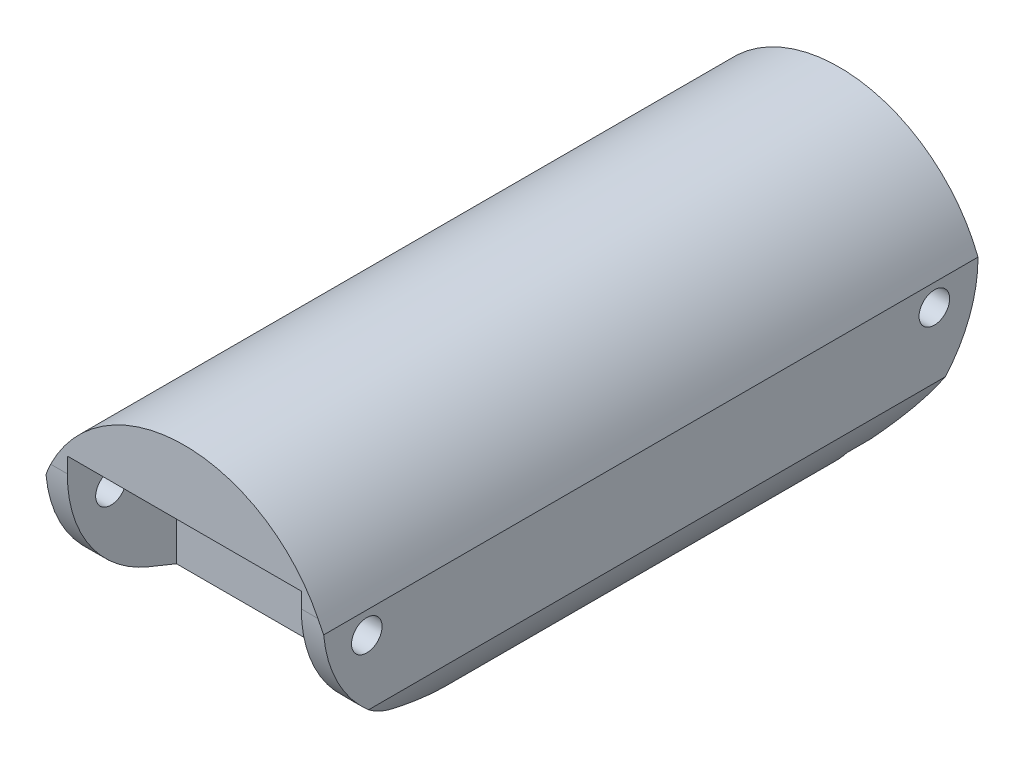
SolidWorks part; units mm, degrees
material "PET"
ref_plane "Front Plane" through (0, 0, 0) normal (0, 0, 1) x (1, 0, 0)
ref_plane "Top Plane" through (0, 0, 0) normal (0, 1, 0) x (1, 0, 0)
ref_plane "Right Plane" through (0, 0, 0) normal (1, 0, 0) x (0, 0, -1)
sketch "Sketch1" plane through (0, 0, 0) normal (0, 0, 1) x (1, 0, 0)
  line L0 (0, 0) -> (0, 5.08)
  line L3 (16.1544, 5.08) -> (16.1544, 0)
  arc A2 (0, 5.08) -> (16.1544, 5.08) centre (8.0772, 1.9574) cw
  arc A3 (0, 0) -> (16.1544, 0) centre (8.0772, 3.1226) ccw
  point P7 (8.0772, -5.5372)
  point P8 (8.0772, 10.6172)
  dimension "D1" = 16.1544
  dimension "D2" = 16.1544
  dimension "D3" = 5.08
extrude "Boss-Extrude1" add sketch "Sketch1" along normal mid plane 38.1 contours A2 L3 A3 L0
sketch "Sketch2" plane through (0, 0, 0) normal (1, 0, 0) x (0, 0, -1)
  line L4 (15.875, 2.54) -> (-49984.125, 2.54) construction
  line L5 (19.05, 5.08) -> (19.05, 0) construction
  line L6 (-19.05, 5.08) -> (-19.05, 0) construction
  line L7 (-19.05, -5.5372) -> (-19.05, 0.635)
  line L8 (-3.81, -5.5372) -> (-19.05, -5.5372)
  line L9 (-19.05, 0.635) -> (-3.81, -5.5372)
  line L10 (0, -1000) -> (0, 49000) construction
  line L18 (19.05, 0.635) -> (19.05, -5.5372)
  line L19 (-16.51, 1.27) -> (-19.05, 1.27)
  line L21 (-16.51, 3.81) -> (-19.05, 3.81)
  line L22 (-19.05, 1.27) -> (-19.05, 3.81)
  line L23 (-15.0884, 2.54) -> (-19.05, 3.81) construction
  line L24 (-15.0884, 2.54) -> (-19.05, 1.27) construction
  line L27 (16.51, 1.27) -> (19.05, 1.27)
  line L28 (19.05, 1.27) -> (19.05, 3.81)
  line L29 (16.51, 3.81) -> (19.05, 3.81)
  line L30 (19.05, -5.5372) -> (8.3594, -5.5372)
  line L31 (-19.05, -5.5372) -> (19.05, -5.5372) construction
  line L32 (8.3594, -5.5372) -> (19.05, 0.635)
  line L33 (-19.05, 10.6172) -> (-19.05, 5.08) construction
  arc A3 (-16.51, 3.81) -> (-16.51, 1.27) centre (-14.3103, 2.54) cw
  arc A4 (16.51, 3.81) -> (16.51, 1.27) centre (14.3103, 2.54) ccw
  point P0 (-15.0884, 2.54)
  point P11 (19.05, 2.54)
  point P14 (-19.05, 2.54)
  point P26 (-19.05, 2.54)
  dimension "D3" = 2.54
  dimension "D4" = 0.635
  dimension "D5" = 60
  dimension "D6" = 0.635
  dimension "D1" = 3.81
extrude "Cut-Extrude1" cut sketch "Sketch2" along normal through all
sketch "Sketch3" plane through (0, 0, 19.05) normal (0, 0, 1) x (1, 0, 0)
  line L3 (-11.7804, 2.54) -> (36.5812, 2.54) construction
  line L4 (8.0772, 9.0576) -> (8.0772, -5.5372) construction
  line L5 (16.1544, 2.54) -> (0, 2.54) construction
  line L6 (16.1544, 2.54) -> (0, 2.54) construction
  line L7 (0, 5.08) -> (0, 0) construction
  line L8 (16.1544, 0.635) -> (0, 0.635) construction
  arc A7 (0, 0) -> (16.1544, 0) centre (8.0772, 3.1226) ccw construction
  arc A9 (14.6124, 0.635) -> (1.542, 0.635) centre (8.0772, 2.54) cw
  arc A13 (5.4577, -3.743) -> (10.6967, -3.743) centre (8.0772, -5.5372) cw
  dimension "D1" = 1.27
  dimension "D2" = 3.175
extrude "Cut-Extrude2" cut sketch "Sketch3" against normal through all contours A13 A9
sketch "Sketch4" plane through (0, 0, 0) normal (-1, 0, 0) x (0, 0, 1)
  line L0 (19.05, 1.27) -> (16.51, 1.27) construction
  line L1 (16.51, 3.81) -> (19.05, 3.81) construction
  line L2 (-16.51, 1.27) -> (-19.05, 1.27) construction
  line L3 (-19.05, 3.81) -> (-16.51, 3.81) construction
  line L4 (19.05, 1.27) -> (16.51, 1.27)
  line L5 (16.51, 3.81) -> (19.05, 3.81)
  line L6 (-16.51, 1.27) -> (-19.05, 1.27)
  line L7 (-19.05, 3.81) -> (-16.51, 3.81)
  line L8 (-19.05, 3.81) -> (-19.05, 1.27)
  line L9 (19.05, 3.81) -> (19.05, 1.27)
  arc A0 (14.3103, 0) -> (16.51, 1.27) centre (14.3103, 2.54) ccw construction
  arc A1 (16.51, 3.81) -> (14.3103, 5.08) centre (14.3103, 2.54) ccw construction
  arc A2 (14.3103, 5.08) -> (14.3103, 0) centre (14.3103, 2.54) ccw construction
  arc A3 (-16.51, 1.27) -> (-14.3103, 0) centre (-14.3103, 2.54) ccw construction
  arc A4 (-14.3103, 5.08) -> (-16.51, 3.81) centre (-14.3103, 2.54) ccw construction
  arc A5 (-14.3103, 0) -> (-14.3103, 5.08) centre (-14.3103, 2.54) ccw construction
  arc A6 (14.3103, 0) -> (16.51, 1.27) centre (14.3103, 2.54) ccw
  arc A7 (16.51, 3.81) -> (14.3103, 5.08) centre (14.3103, 2.54) ccw
  arc A8 (14.3103, 5.08) -> (14.3103, 0) centre (14.3103, 2.54) ccw
  arc A9 (-16.51, 1.27) -> (-14.3103, 0) centre (-14.3103, 2.54) ccw
  arc A10 (-14.3103, 5.08) -> (-16.51, 3.81) centre (-14.3103, 2.54) ccw
  arc A11 (-14.3103, 0) -> (-14.3103, 5.08) centre (-14.3103, 2.54) ccw
extrude "Boss-Extrude2" add sketch "Sketch4" against normal up to surface (16.1544 mm away) up to face at (16.1544, 2.54, 0)
ref_plane "Plane1" through (5.08, 0, 0) normal (-1, 0, 0) x (0, 0, 1)
ref_plane "Plane2" through (8.0772, 0, 0) normal (1, 0, 0) x (0, 0, -1)
sketch "Sketch7" plane through (5.08, 0, 0) normal (-1, 0, 0) x (0, 0, 1)
  line L0 (-19.05, 0) -> (-19.05, 2.8575)
  line L1 (-19.05, 0.635) -> (-19.05, 5.08) construction
  line L2 (-19.05, 2.8575) -> (-16.51, 2.8575)
  line L4 (17.4821, 0) -> (-17.9501, 0) construction
  line L5 (-16.51, 0) -> (-19.05, 0)
  line L6 (-19.05, 2.8575) -> (-19.05, 0) construction
  line L7 (-16.51, 0) -> (-19.05, 0) construction
  line L8 (-16.51, 2.8575) -> (-16.51, 0)
  dimension "D1" = 2.54
extrude "Cut-Extrude3" cut sketch "Sketch7" along normal blind 2.54
sketch "Sketch9" plane through (0, 2.8575, 0) normal (0, -1, 0) x (1, 0, 0)
  line L0 (2.54, -16.51) -> (2.54, -19.05) construction
  line L1 (5.08, -19.05) -> (2.54, -19.05)
  line L2 (5.08, -19.05) -> (5.08, -15.24)
  line L3 (5.08, -15.24) -> (2.54, -15.24)
  line L4 (2.54, -19.05) -> (2.54, -15.24)
  line L5 (5.08, -16.51) -> (5.08, -19.05) construction
  line L6 (2.54, -19.05) -> (5.08, -19.05) construction
  dimension "D1" = 3.81
extrude "Cut-Extrude5" cut sketch "Sketch9" along normal through all
sketch "Sketch11" plane through (0, 2.8575, 0) normal (0, -1, 0) x (1, 0, 0)
  line L4 (5.08, -19.05) -> (5.08, -15.24)
  line L5 (5.08, -15.24) -> (2.54, -15.24)
  line L6 (2.54, -15.24) -> (2.54, -19.05)
  line L7 (2.54, -19.05) -> (5.08, -19.05)
  line L8 (5.08, -19.05) -> (5.08, -15.24)
  line L9 (5.08, -15.24) -> (2.54, -15.24)
  line L10 (2.54, -15.24) -> (2.54, -19.05)
  line L11 (2.54, -19.05) -> (5.08, -19.05)
  dimension "D1" = 0
extrude "Cut-Extrude8" cut sketch "Sketch11" against normal blind 2.54
sketch "Sketch12" plane through (2.54, 0, 0) normal (1, 0, 0) x (0, 0, -1)
  line L4 (15.24, -1.5647) -> (19.05, 0.635)
  line L5 (19.05, 0.635) -> (19.05, 5.3975)
  line L6 (19.05, 5.3975) -> (15.24, 5.3975)
  line L7 (15.24, 5.3975) -> (15.24, -1.5647)
  line L8 (15.24, -1.5647) -> (19.05, 0.635)
  line L10 (19.05, 0.635) -> (19.05, 5.3975)
  line L11 (19.05, 5.3975) -> (15.24, 5.3975)
  line L12 (15.24, 5.3975) -> (15.24, -1.5647)
  dimension "D1" = 0
extrude "Cut-Extrude9" cut sketch "Sketch12" against normal blind 1.27
sketch "Sketch13" plane through (0, 0, -15.24) normal (0, 0, -1) x (-1, 0, 0)
  line L2 (-5.08, 5.3975) -> (-5.08, -0.5842)
  line L3 (-5.08, 0.635) -> (-5.08, -1.5647) construction
  line L4 (-5.08, -1.5647) -> (-1.27, -1.5647)
  line L5 (-1.27, -1.5647) -> (-1.27, 5.3975)
  line L6 (-1.27, 5.3975) -> (-5.08, 5.3975)
  line L7 (-5.08, 5.3975) -> (-5.08, -1.5647)
  line L10 (-1.27, 5.3975) -> (-5.08, 5.3975)
  line L13 (-5.08, -0.5842) -> (-1.27, -0.5842)
  line L14 (-1.27, -1.5647) -> (-1.27, 0.635) construction
  line L15 (-1.27, -0.5842) -> (-1.27, 5.3975)
  line M6 (-1.27, -1.5647) -> (-1.27, 5.3975)
  line M7 (-1.27, 5.3975) -> (-5.08, 5.3975)
  line M12 (-5.08, 5.3975) -> (-5.08, -1.5647)
  dimension "D2" = 0.5842
  dimension "D1" = 0
extrude "Cut-Extrude10" cut sketch "Sketch13" against normal blind 1.27 contours L13 M12 M6 M7
sketch "Sketch14" plane through (0, 5.3975, 0) normal (0, -1, 0) x (1, 0, 0)
  line L2 (16.1544, -19.05) -> (16.1544, -17.9501) construction
  line L4 (1.27, -19.05) -> (5.08, -19.05)
  line L5 (5.08, -19.05) -> (5.08, -13.97)
  line L6 (5.08, -13.97) -> (1.27, -13.97)
  line L7 (1.27, -13.97) -> (1.27, -19.05)
  line L8 (1.27, -19.05) -> (14.8844, -19.05)
  line L9 (14.8844, -19.05) -> (14.8844, -12.7)
  line L10 (14.8844, -12.7) -> (1.27, -12.7)
  line L11 (1.27, -12.7) -> (1.27, -19.05)
  line M5 (1.27, -19.05) -> (5.08, -19.05)
  line M6 (5.08, -19.05) -> (5.08, -13.97)
  line M8 (1.27, -13.97) -> (1.27, -19.05)
  line M13 (5.08, -13.97) -> (1.27, -13.97)
  dimension "D2" = 6.35
  dimension "D3" = 1.27
  dimension "D1" = 0
extrude "Cut-Extrude11" cut sketch "Sketch14" along normal up to next and the other way blind 1.27 contours M8 M5 M6 M13 | L8 L9 L10 L11 region at (3.175, 5.3975, -16.51)
mirror "Mirror3" about plane through (0, 0, 0) normal (0, 0, 1) of "Cut-Extrude9", "Cut-Extrude5", "Cut-Extrude3", "Cut-Extrude8", "Cut-Extrude10", "Cut-Extrude11"
sketch "Sketch10" plane through (0, 0, 0) normal (-1, 0, 0) x (0, 0, 1)
  line L0 (-19.05, 3.81) -> (-19.05, 0) construction
  line L1 (-19.05, 0.635) -> (-19.05, 5.08) construction
  line L2 (-19.05, 0) -> (-16.3757, 0) construction
  line L4 (17.4821, 0) -> (-17.9501, 0) construction
  circle A1 centre (-16.51, 3.81) radius 0.889
  dimension "D1" = 2.54
  dimension "D2" = 1.778
  dimension "D4" = 3.81
extrude "Cut-Extrude7" cut sketch "Sketch10" against normal through all
ref_plane "Plane3" through (0, 0, 0) normal (0, 0, -1) x (-1, 0, 0)
sketch "Sketch16" plane through (0, 0, -12.7) normal (0, 0, -1) x (-1, 0, 0)
  line L0 (-10.7442, 6.3754) -> (-5.4102, 6.3754)
  line L1 (-10.7442, 0.6858) -> (-5.4102, 0.6858)
  line L2 (-10.7442, 0.6858) -> (-10.7442, 6.3754)
  line L4 (-5.4102, 0.6858) -> (-5.4102, 6.3754)
  line L5 (-10.7442, 0.6858) -> (-5.4102, 6.3754) construction
  line L6 (-10.7442, 6.3754) -> (-5.4102, 0.6858) construction
  line L7 (-6.0452, 5.9944) -> (-5.4102, 5.9944) construction
  line L8 (-6.0452, 6.3754) -> (-5.4102, 6.3754)
  line L9 (-6.0452, 5.6134) -> (-5.4102, 5.6134)
  line L10 (-14.7786, -2.3622) -> (-1.3758, -2.3622) construction
  arc A0 (-6.1277, -3.0312) -> (-10.0267, -3.0312) centre (-8.0772, -5.5372) ccw construction
  arc A1 (-6.0452, 6.3754) -> (-6.0452, 5.6134) centre (-6.0452, 5.9944) ccw
  arc A2 (-5.4102, 5.6134) -> (-5.4102, 6.3754) centre (-5.4102, 5.9944) ccw
  arc A3 (-14.8844, -2.2303) -> (-14.1701, -3.0312) centre (-8.0772, 3.1226) ccw construction
  arc A4 (-1.9843, -3.0312) -> (-1.27, -2.2303) centre (-8.0772, 3.1226) ccw construction
  point P0 (-8.0772, 3.5306)
  point P9 (-8.0772, -2.3622)
  point P11 (-5.7277, 5.9944)
  dimension "D1" = 5.6896
  dimension "D2" = 5.334
  dimension "D3" = 0.762
  dimension "D4" = 0.635
  dimension "D5" = 3.048
extrude "Cut-Extrude12" cut sketch "Sketch16" against normal blind 15.875 contours L9 A2 L8 A1
sketch "Sketch20" plane through (0, 0, 12.7) normal (0, 0, 1) x (1, 0, 0)
  line L1 (5.4102, 0.6858) -> (10.7442, 0.6858) construction
  line L2 (5.4102, 0.6858) -> (5.4102, 6.3754) construction
  line L3 (5.4102, 6.3754) -> (10.7442, 6.3754) construction
  line L4 (10.7442, 0.6858) -> (10.7442, 6.3754) construction
  line L5 (5.4102, 0.6858) -> (10.7442, 6.3754) construction
  line L6 (5.4102, 6.3754) -> (10.7442, 0.6858) construction
  line L7 (8.0772, -2.3622) -> (15.7288, -2.3622) construction
  line L8 (10.1092, 5.9944) -> (10.7442, 5.9944) construction
  line L9 (10.1092, 6.3754) -> (10.7442, 6.3754)
  line L10 (10.1092, 5.6134) -> (10.7442, 5.6134)
  arc A2 (10.1092, 6.3754) -> (10.1092, 5.6134) centre (10.1092, 5.9944) ccw
  arc A3 (10.7442, 5.6134) -> (10.7442, 6.3754) centre (10.7442, 5.9944) ccw
  arc A4 (10.6967, -3.743) -> (5.4577, -3.743) centre (8.0772, -5.5372) ccw construction
  point P0 (8.0772, 3.5306)
  point P18 (10.4267, 5.9944)
  dimension "D1" = 3.048
  dimension "D2" = 5.6896
  dimension "D3" = 5.334
  dimension "D4" = 0.635
  dimension "D5" = 0.762
extrude "Cut-Extrude13" cut sketch "Sketch20" against normal blind 15.875
fillet "Fillet1" radius 7.62 4 edges at (15.5194, 0.635, -19.05) (0.635, 0.635, -19.05) (15.5194, 0.635, 19.05) (0.635, 0.635, 19.05)
sketch "Sketch21" plane through (0, 0, 0) normal (-1, 0, 0) x (0, 0, 1)
  text T0 "Mid 2\r\n"
extrude "Cut-Extrude14" cut sketch "Sketch21" against normal blind 1
mirror "Mirror4" about plane through (0, 0, 0) normal (0, 0, -1) of "Cut-Extrude7"
equation "\"D1@Sketch1\"=0.636"
equation "\"D2@Sketch1\"=0.636"
equation "\"D1@Boss-Extrude1\"=1.5"
equation "\"D2@Sketch2\"=0.1"
equation "\"D3@Sketch2\"=0.1"
